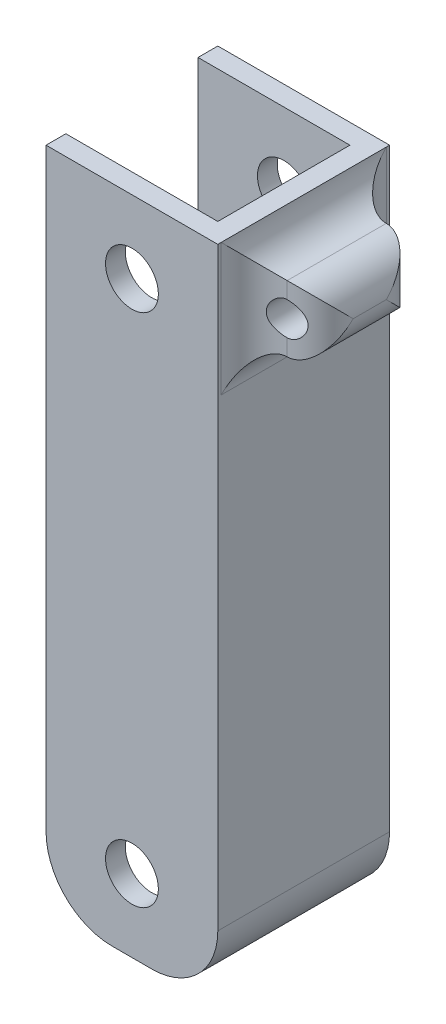
SolidWorks part; units mm, degrees
ref_plane "Front Plane" through (0, 0, 0) normal (0, 0, 1) x (1, 0, 0)
ref_plane "Top Plane" through (0, 0, 0) normal (0, 1, 0) x (1, 0, 0)
ref_plane "Right Plane" through (0, 0, 0) normal (1, 0, 0) x (0, 0, -1)
sketch "Sketch1" plane through (0, 0, 0) normal (1, 0, 0) x (0, 0, -1)
  line L1 (-13, 0) -> (13, 0)
  line L2 (-13, 0) -> (-13, 100)
  line L3 (-13, 100) -> (13, 100)
  line L4 (13, 0) -> (13, 100)
  point P4 (0, 0)
  dimension "D1" = 26
  dimension "D2" = 100
extrude "Boss-Extrude1" add sketch "Sketch1" along normal mid plane 26
sketch "Sketch3" plane through (0, 0, 0) normal (0, 0, 1) x (1, 0, 0)
  line L0 (13, 0) -> (-13, 0) construction
  line L1 (13, 100) -> (-13, 100) construction
  circle A0 centre (0, 11) radius 4
  circle A1 centre (0, 89) radius 4
  dimension "D1" = 8
  dimension "D3" = 11
  dimension "D2" = 11
fillet "Fillet1" radius 10 2 edges at (13, 0, 0) (-13, 0, 0)
sketch "Sketch5" plane through (0, 0, 0) normal (0, 0, 1) x (1, 0, 0)
  line L0 (13, 95) -> (23, 95)
  line L1 (13, 100) -> (13, 10) construction
  line L2 (23, 95) -> (23, 85)
  line L3 (23, 85) -> (13, 85)
  line L4 (13, 100) -> (-13, 100) construction
  line L5 (13, 95) -> (13, 85)
  circle A0 centre (18, 90) radius 2.5
  point P11 (18, 95)
  point P13 (23, 90)
  dimension "D4" = 5
  dimension "D1" = 10
  dimension "D2" = 10
  dimension "D3" = 5
extrude "Boss-Extrude3" add sketch "Sketch5" along normal mid plane 15
fillet "Fillet2" radius 5 8 edges at (23, 90, -7.5) (23, 90, 7.5) (13, 90, 7.5) (13, 90, -7.5) (13, 95, 0) (23, 95, 0) (23, 85, 0) (13, 85, 0)
sketch "Sketch6" plane through (0, 100, 0) normal (0, 1, 0) x (1, 0, 0)
  line L0 (-13, 10) -> (10, 10)
  line L1 (-13, 13) -> (-13, -13) construction
  line L2 (10, 10) -> (10, -10)
  line L3 (10, -10) -> (-13, -10)
  line L4 (13, 13) -> (-13, 13) construction
  line L5 (13, 12.5) -> (13, -12.5) construction
  line L6 (13, -13) -> (-13, -13) construction
  line L7 (-13, 10) -> (-13, -10)
  dimension "D1" = 3
  dimension "D2" = 3
  dimension "D3" = 3
extrude "Cut-Extrude1" cut sketch "Sketch6" against normal through all both and the other way through all
extrude "Cut-Extrude2" cut sketch "Sketch3" against normal through all both and the other way through all
equation "\"D2@Sketch6\"=\"D1@Sketch6\""
equation "\"D3@Sketch6\"=\"D1@Sketch6\""
